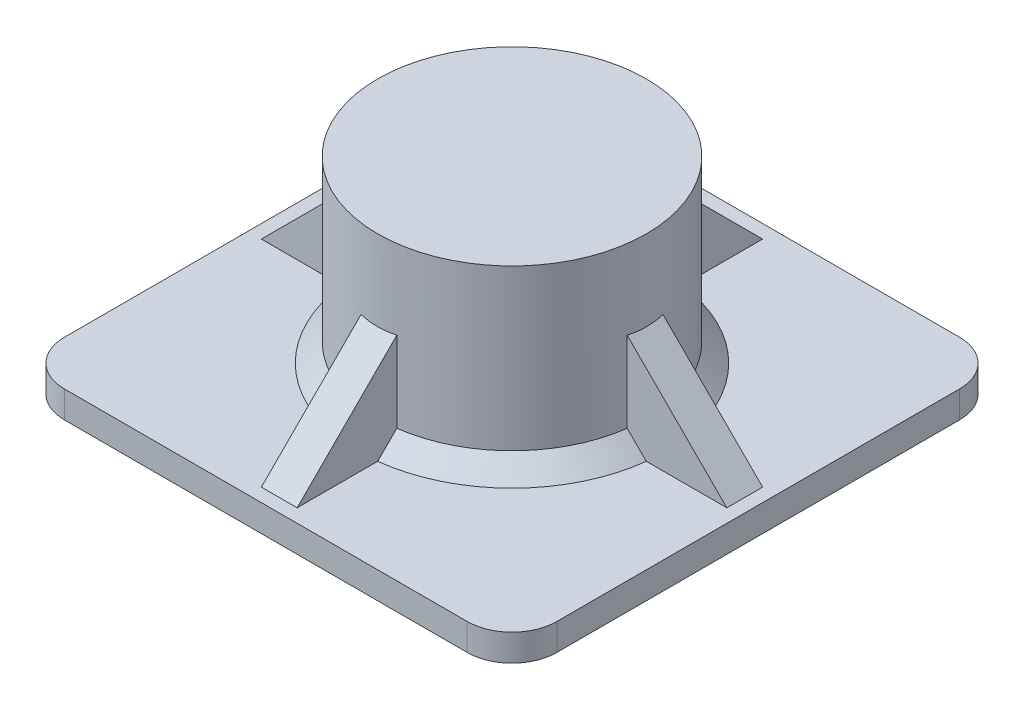
SolidWorks part; units mm, degrees
ref_plane "Front Plane" through (0, 0, 0) normal (0, 0, 1) x (1, 0, 0)
ref_plane "Top Plane" through (0, 0, 0) normal (0, 1, 0) x (1, 0, 0)
ref_plane "Right Plane" through (0, 0, 0) normal (1, 0, 0) x (0, 0, -1)
sketch "Sketch1" plane through (0, 0, 0) normal (0, 1, 0) x (1, 0, 0)
  line L1 (27.5, 27.5) -> (-27.5, 27.5)
  line L2 (27.5, 27.5) -> (27.5, -27.5)
  line L3 (27.5, -27.5) -> (-27.5, -27.5)
  line L4 (-27.5, 27.5) -> (-27.5, -27.5)
  line L5 (27.5, 27.5) -> (-27.5, -27.5) construction
  line L6 (27.5, -27.5) -> (-27.5, 27.5) construction
  point P0 (0, 0)
  dimension "D1" = 55
extrude "Boss-Extrude1" add sketch "Sketch1" along normal blind 3
sketch "Sketch2" plane through (0, 0, 0) normal (0, 0, 1) x (1, 0, 0)
  line L0 (0, 3) -> (0, 23)
  line L1 (-27.5, 3) -> (27.5, 3) construction
  line L2 (0, 23) -> (15, 23)
  line L3 (15, 23) -> (15, 5.1213)
  line L4 (15, 5.1213) -> (17.1213, 3)
  line L5 (17.1213, 3) -> (0, 3)
  dimension "D1" = 20
  dimension "D2" = 15
  dimension "D3" = 45
  dimension "D4" = 3
revolve "Revolve1" add sketch "Sketch2" angle 360 about L0
sketch "Sketch3" plane through (0, 0, 0) normal (1, 0, 0) x (0, 0, -1)
  line L0 (0, 3) -> (10, 3) construction
  line L3 (-27.5, 3) -> (27.5, 3) construction
  line L4 (10, 3) -> (10, 19)
  line L5 (10, 19) -> (26, 3)
  line L6 (26, 3) -> (10, 3)
  dimension "D1" = 45
  dimension "D2" = 16
  dimension "D3" = 10
extrude "Boss-Extrude2" add sketch "Sketch3" along normal blind 2 and the other way blind 2
ref_axis "Axis1" through (0, 0, 0) along (0, 1, 0)
pattern_circular "CirPattern1" count 4 over 360 about axis through (0, 0, 0) along (0, 1, 0) of "Boss-Extrude2"
fillet "Fillet1" radius 5 4 edges at (-27.5, 1.5, 27.5) (-27.5, 1.5, -27.5) (27.5, 1.5, -27.5) (27.5, 1.5, 27.5)
